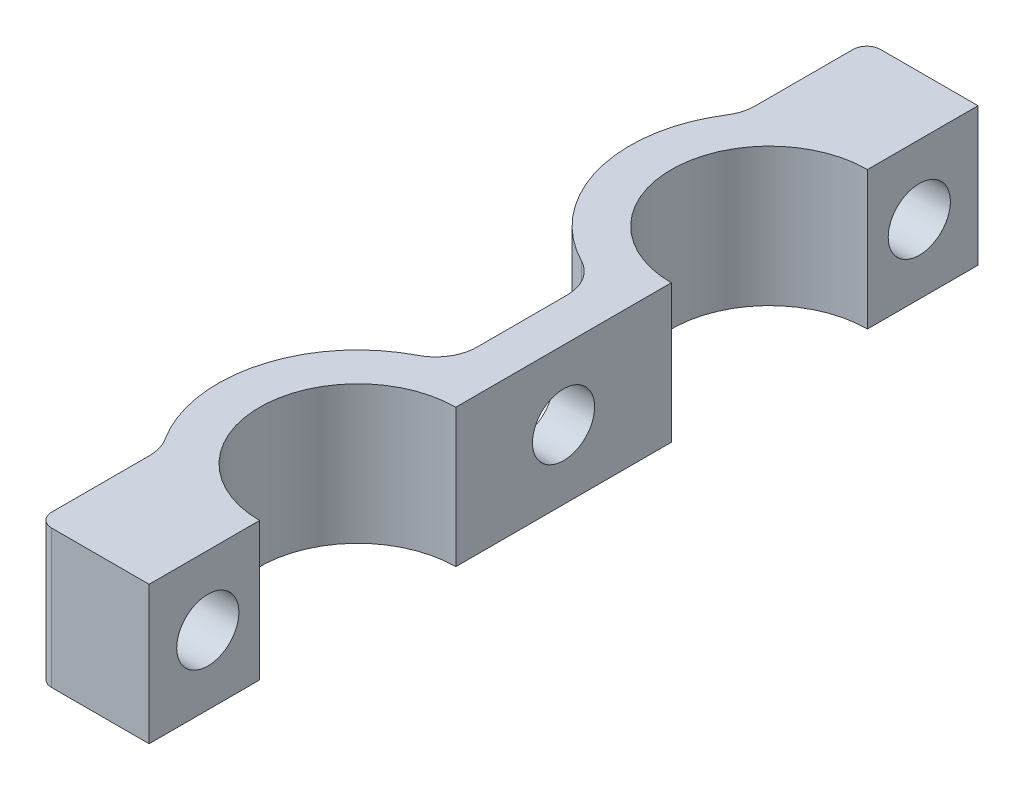
SolidWorks part; units mm, degrees
material "3.1355 (EN-AW 2024)"
ref_plane "Front" through (0, 0, 0) normal (0, 0, 1) x (1, 0, 0)
ref_plane "Top" through (0, 0, 0) normal (0, 1, 0) x (1, 0, 0)
ref_plane "Right" through (0, 0, 0) normal (1, 0, 0) x (0, 0, -1)
sketch "Эскиз1" plane through (0, 0, 0) normal (0, 1, 0) x (1, 0, 0)
  line L0 (0, 0) -> (0, 60) construction
  line L1 (0, 30) -> (-15.0292, 30) construction
  line L2 (0, 0) -> (0, 8)
  line L3 (0, 60) -> (0, 52)
  line L4 (0, 37.8) -> (0, 22.2)
  line L5 (-3, 0) -> (-3, 5.4558)
  line L6 (-3, 35.2558) -> (-3, 24.7442)
  line L7 (-3, 60) -> (-3, 54.5442)
  line L8 (-3, 60) -> (0, 60)
  line L9 (-3, 0) -> (0, 0)
  circle A0 centre (0, 15.1) radius 7.1 construction
  circle A1 centre (0, 44.9) radius 7.1 construction
  arc A2 (0, 8) -> (0, 22.2) centre (0, 15.1) cw
  arc A3 (0, 52) -> (0, 37.8) centre (0, 44.9) ccw
  arc A4 (-3, 5.4558) -> (-3, 24.7442) centre (0, 15.1) cw
  arc A5 (-3, 54.5442) -> (-3, 35.2558) centre (0, 44.9) ccw
  point P9 (0, 22.2)
  dimension "D2" = 15.1
  dimension "D3" = 14.2
  dimension "D1" = 60
  dimension "D4" = 3
extrude "Бобышка-Вытянуть1" add sketch "Эскиз1" along normal blind 10
sketch "Эскиз2" plane through (0, 10, 0) normal (0, 1, 0) x (1, 0, 0)
  line L0 (-3, 60) -> (-8.0498, 60)
  line L1 (-8.0498, 60) -> (-8.0498, 51)
  line L2 (-3, 60) -> (-3, 54.5442)
  line L3 (0, 30) -> (-3, 30) construction
  line L4 (0, 22.2) -> (0, 37.8) construction
  line L5 (-3, 35.2558) -> (-3, 24.7442) construction
  line L6 (-3, 0) -> (-3, 5.4558)
  line L7 (-8.0498, 0) -> (-8.0498, 9)
  line L8 (-3, 0) -> (-8.0498, 0)
  arc A0 (-3, 54.5442) -> (-3, 35.2558) centre (0, 44.9) ccw construction
  arc A1 (-3, 54.5442) -> (-8.0498, 51) centre (0, 44.9) ccw
  arc A2 (-3, 5.4558) -> (-8.0498, 9) centre (0, 15.1) cw
  dimension "D1" = 9
sketch "Эскиз3" plane through (-3, 0, 0) normal (-1, 0, 0) x (0, 0, 1)
  line L0 (-60, 5) -> (-54.7288, 5) construction
  line L1 (-60, 10) -> (-60, 0) construction
  line L3 (-30, 10) -> (-30, 0) construction
  line L4 (-35.2558, 10) -> (-24.7442, 10) construction
  line L5 (-35.2558, 0) -> (-24.7442, 0) construction
  circle A0 centre (-55.75, 5) radius 2.25
  circle A1 centre (-4.25, 5) radius 2.25
  point P6 (-58, 5)
  point P7 (-53.5, 5)
  dimension "D1" = 4.5
  dimension "D2" = 2
extrude "Бобышка-Вытянуть2" add sketch "Эскиз2" against normal up to surface (10 mm away) up to face at (-3.8667, 0, -30)
extrude "Вырез-Вытянуть1" cut sketch "Эскиз3" against normal through all and the other way up to surface (5.0498 mm away) other way up to face at (-8.0498, 5, -55.5)
sketch "Эскиз4" plane through (-3, 0, 0) normal (-1, 0, 0) x (0, 0, 1)
  line L0 (-30, 10) -> (-30, 0) construction
  line L1 (-35.2558, 10) -> (-24.7442, 10) construction
  line L2 (-35.2558, 0) -> (-24.7442, 0) construction
  circle A0 centre (-30, 5) radius 2.25
  dimension "D1" = 4.5
extrude "Вырез-Вытянуть2" cut sketch "Эскиз4" against normal through all
fillet "Скругление1" radius 3 4 edges at (-8.0498, 5, -9) (-8.0498, 5, -51) (-3, 5, -35.2558) (-3, 5, -24.7442)
fillet "Скругление2" radius 1 2 edges at (-8.0498, 5, -60) (-8.0498, 5, 0)
equation "\"D2@Эскиз1\"=8+\"D3@Эскиз1\"/2"
